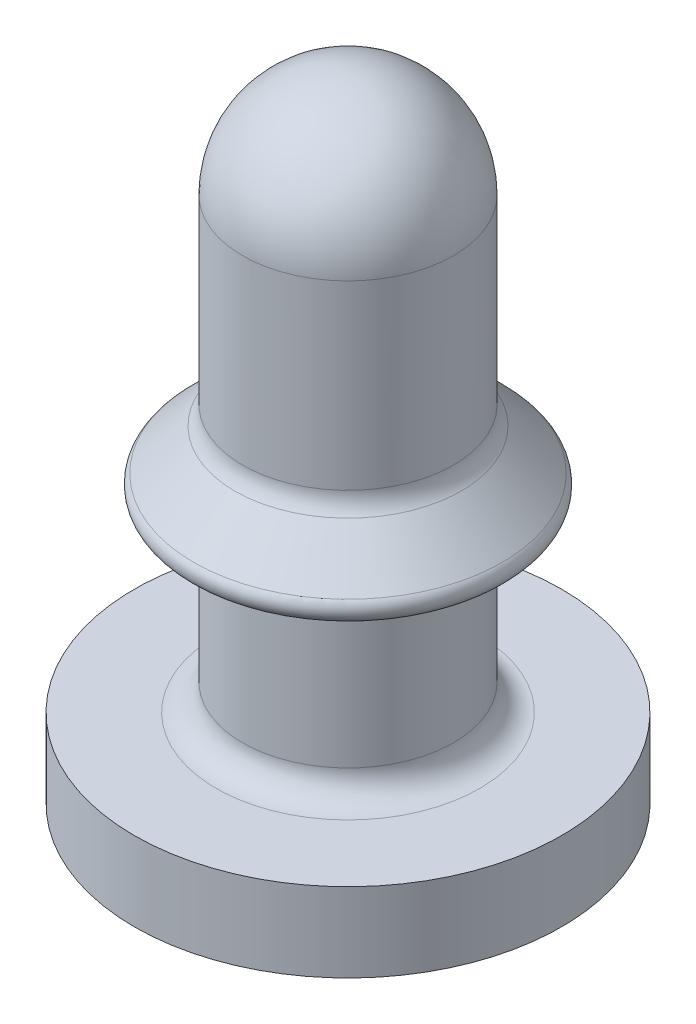
SolidWorks part; units mm, degrees
ref_plane "Front Plane" through (0, 0, 0) normal (0, 0, 1) x (1, 0, 0)
ref_plane "Top Plane" through (0, 0, 0) normal (0, 1, 0) x (1, 0, 0)
ref_plane "Right Plane" through (0, 0, 0) normal (1, 0, 0) x (0, 0, -1)
sketch "Sketch1" plane through (0, 0, 0) normal (0, 1, 0) x (1, 0, 0)
  circle A0 centre (0, 0) radius 2
  dimension "D1" = 4
extrude "Boss-Extrude1" add sketch "Sketch1" along normal blind 12
sketch "Sketch6" plane through (0, 0, 0) normal (0, -1, 0) x (1, 0, 0)
  circle A0 centre (0, 0) radius 4.05
  dimension "D1" = 8.1
extrude "Boss-Extrude3" add sketch "Sketch6" against normal blind 1.5
sketch "Sketch8" plane through (0, 0, 0) normal (0, 0, 1) x (1, 0, 0)
  line L0 (2, 6.3536) -> (2.9268, 5.4268)
  line L1 (2, 1.5) -> (2, 12) construction
  line L2 (2.75, 5) -> (2, 5)
  line L3 (2, 5) -> (2, 6.3536)
  line L5 (4.05, 1.5) -> (-4.05, 1.5) construction
  line L6 (0, 0) -> (0, 12) construction
  line L7 (-4.05, 0) -> (4.05, 0) construction
  line L8 (2, 12) -> (-2, 12) construction
  arc A0 (2.75, 5) -> (2.9268, 5.4268) centre (2.75, 5.25) ccw
  dimension "D3" = 0.5
  dimension "D4" = 6
  dimension "D1" = 3.5
  dimension "D2" = 45
revolve "Revolve1" add sketch "Sketch8" angle 360 about L6
sketch "Sketch2" plane through (0, 0, 0) normal (0, -1, 0) x (1, 0, 0)
  circle A0 centre (0, 0) radius 1
  dimension "D1" = 2
extrude "Cut-Extrude1" cut sketch "Sketch2" against normal blind 10
draft "Draft1" type of draft neutral plane draft angle 1 faces to draft 1 face at (0, 10, -1) neutral plane through (0, 10, 0) neutral plane normal (0, -1, 0) parameters "D1"=1
sketch "Sketch7" plane through (0, 0, 0) normal (0, 0, 1) x (1, 0, 0)
  line L0 (2, 6.3536) -> (2, 12) construction
  line L1 (2, 12) -> (-2, 12) construction
  line L4 (0, 10) -> (0, 12) construction
  line L5 (2, 10) -> (3.0807, 10)
  line L6 (3.0807, 10) -> (3.0807, 13.0807)
  line L7 (3.0807, 13.0807) -> (0, 13.0807)
  line L8 (0, 13.0807) -> (0, 12)
  arc A0 (2, 10) -> (0, 12) centre (0, 10) ccw
  dimension "D1" = 3.0807
revolve "Cut-Revolve3" cut sketch "Sketch7" angle 360 about L4
sketch "Sketch3" plane through (0, 10, 0) normal (0, -1, 0) x (1, 0, 0)
  line L0 (1.151, 0.2338) -> (0.746, 0)
  line L1 (0.746, 0) -> (1.151, -0.2338)
  line L2 (0, 0) -> (1.1746, 0) construction
  line L3 (1.151, 0.2338) -> (1.151, -0.2338) construction
  line L6 (-0.373, -1.1138) -> (-0.373, -0.6461)
  line L7 (-0.373, -0.6461) -> (-0.778, -0.8799)
  line L10 (-0.373, -1.1138) -> (-0.778, -0.8799) construction
  line L11 (-0.778, 0.8799) -> (-0.373, 0.6461)
  line L14 (-0.373, 0.6461) -> (-0.373, 1.1138)
  line L15 (-0.778, 0.8799) -> (-0.373, 1.1138) construction
  arc A1 (-0.778, -0.8799) -> (-0.373, -1.1138) centre (0, 0) ccw
  arc A2 (-0.373, 1.1138) -> (-0.778, 0.8799) centre (0, 0) ccw
  circle A7 centre (0, 0) radius 1.1746 construction
  arc A8 (1.151, -0.2338) -> (1.151, 0.2338) centre (0, 0) ccw
  circle A9 centre (0, 0) radius 1 construction
  point P16 (0, 0)
  dimension "D1" = 0.254
extrude "Boss-Extrude2" add sketch "Sketch3" along normal up to surface (10 mm away) up to face at (0, 0, 1.1746)
sketch "ref_for_revolve" plane through (0, 0, 0) normal (0, -1, 0) x (1, 0, 0)
  circle A0 centre (0, 0) radius 1.1746 construction
sketch "Sketch4" plane through (0, 0, 0) normal (0, 0, 1) x (1, 0, 0)
  line L1 (1.1746, 0) -> (0.746, 0.4286)
  line L2 (0.746, 0.4286) -> (0, 0.4286)
  line L4 (0, 0.4286) -> (0, 0)
  line L5 (0.746, 0.4286) -> (0.746, 0) construction
  line L6 (0.746, 0) -> (1.1746, 0) construction
  line L7 (1.1746, 0) -> (0, 0)
  line L8 (-0.373, 0) -> (1.151, 0) construction
  line L9 (-1.1746, 0) -> (1.1746, 0) construction
revolve "Cut-Revolve1" cut sketch "Sketch4" angle 360 about L4
fillet "Fillet1" radius 0.5 3 edges at (0, 1.5, -2) (0, 5, -2) (0, 6.3536, -2)
